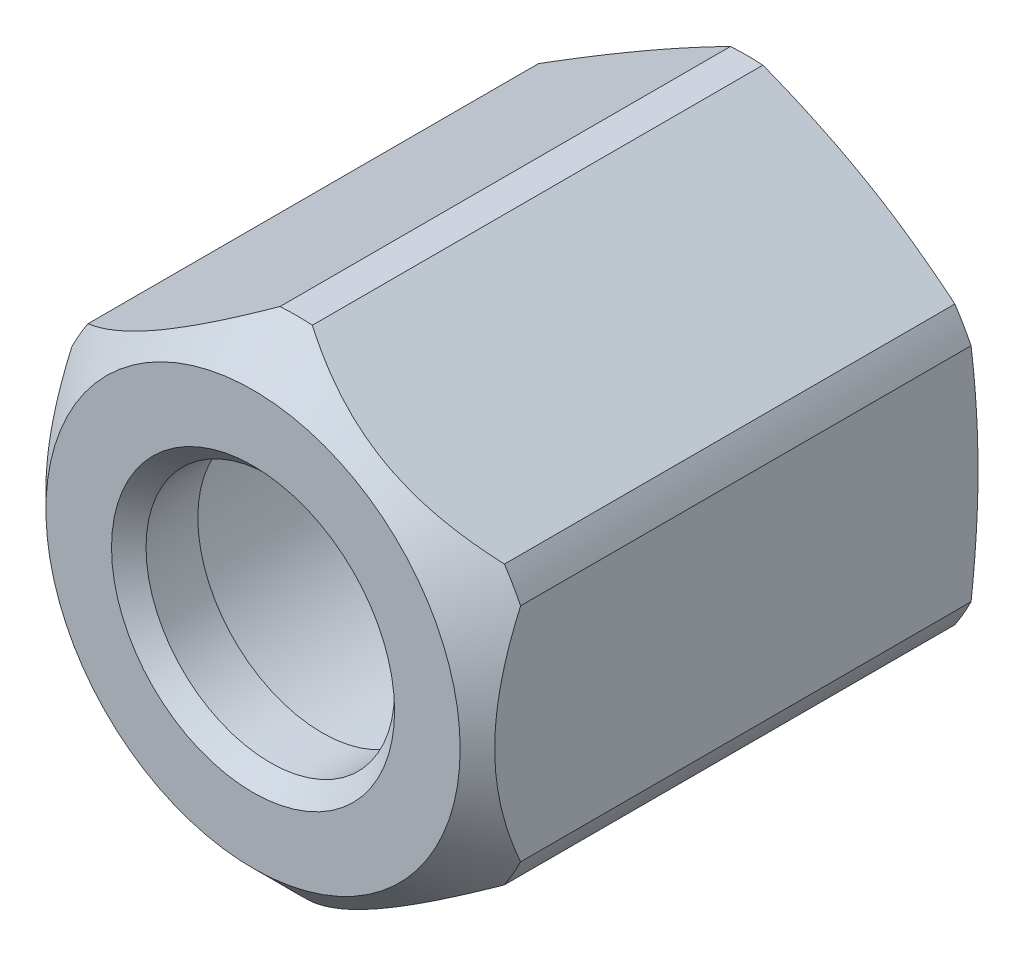
SolidWorks part; units mm, degrees
ref_plane "Ebene vorne" through (0, 0, 0) normal (0, 0, 1) x (1, 0, 0)
ref_plane "Ebene oben" through (0, 0, 0) normal (0, 1, 0) x (1, 0, 0)
ref_plane "Ebene rechts" through (0, 0, 0) normal (1, 0, 0) x (0, 0, -1)
sketch "Skizze1" plane through (0, 0, 0) normal (1, 0, 0) x (0, 0, -1)
  line L0 (0, 4.1) -> (0.5, 3.6)
  line L1 (0.5, 3.6) -> (2, 3.6)
  line L2 (2, 3.6) -> (2, 4.9)
  line L3 (2, 4.9) -> (10.8, 4.9)
  line L4 (10.8, 4.9) -> (10.8, 4.4585)
  line L5 (10.8, 4.4585) -> (13.9585, 4.4585)
  line L6 (13.9585, 4.4585) -> (14.5, 5)
  line L7 (14.5, 5) -> (14.5, 6.5)
  line L8 (14.5, 6.5) -> (14.299, 7.25)
  line L9 (14.299, 7.25) -> (1.25, 7.25)
  line L10 (1.25, 7.25) -> (0, 6)
  line L11 (0, 6) -> (0, 4.1)
  line L12 (14.5, 0) -> (0, 0) construction
revolve "Rotation1" add sketch "Skizze1" angle 360 about L12 reverse direction yes
cosmetic thread "Gewindedarstellung1" parameters "D1"=3.7, "D2"=10
sketch "Skizze2" plane through (0, 0, 0) normal (0, 0, 1) x (1, 0, 0)
  line L0 (-34.75, -33.8333) -> (32.5833, -33.8333)
  line L1 (32.5833, -33.8333) -> (32.5833, 34.1667)
  line L2 (32.5833, 34.1667) -> (-34.75, 34.1667)
  line L3 (-34.75, 34.1667) -> (-34.75, -33.8333)
  line L4 (-6.5, -3.7528) -> (0, -7.5056)
  line L5 (0, -7.5056) -> (6.5, -3.7528)
  line L6 (6.5, -3.7528) -> (6.5, 3.7528)
  line L7 (6.5, 3.7528) -> (0, 7.5056)
  line L8 (0, 7.5056) -> (-6.5, 3.7528)
  line L9 (-6.5, 3.7528) -> (-6.5, -3.7528)
extrude "Schnitt-Linear austragen1" cut sketch "Skizze2" along normal blind 30 and the other way blind 30
ref_plane "Ebene1" through (0, 0, -21.9) normal (0, 0, 1) x (1, 0, 0)
ref_plane "Ebene2" through (0, 0, -17.5) normal (0, 0, 1) x (1, 0, 0)
ref_plane "Ebene3" through (0, 0, -2) normal (0, 0, 1) x (1, 0, 0)
ref_plane "Ebene4" through (0, 0, -10.4) normal (0, 0, 1) x (1, 0, 0)
ref_plane "Ebene5" through (0, 0, 9.1) normal (0, 0, 1) x (1, 0, 0)
ref_plane "MUTTER XY" through (0, 0, 9.1) normal (0, 0, 1) x (1, 0, 0)
ref_plane "MUTTER XZ" through (0, 0, 0) normal (0, -1, 0) x (-1, 0, 0)
ref_plane "MUTTER YZ" through (0, 0, 0) normal (1, 0, 0) x (0, 0, -1)
ref_axis "MUTTER X" through (-80.9, 0, 9.1) along (1, 0, 0)
ref_axis "MUTTER Y" through (0, -50, 9.1) along (0, 1, 0)
ref_axis "MUTTER Z" through (0, 0, 80.9) along (0, 0, -1)
sketch3d "MUTTER"
  point P0 (0, 0, 9.1)
ref_plane "TO_DUMMY XY" through (0, 0, 0) normal (0, 1, 0) x (1, 0, 0)
ref_plane "TO_DUMMY XZ" through (0, 0, 0) normal (0, 0, 1) x (1, 0, 0)
ref_plane "TO_DUMMY YZ" through (0, 0, 0) normal (1, 0, 0) x (0, 0, -1)
ref_axis "TO_DUMMY X" through (-80.9, 0, 0) along (1, 0, 0)
ref_axis "TO_DUMMY Y" through (0, 0, 50) along (0, 0, -1)
ref_axis "TO_DUMMY Z" through (0, 50, 0) along (0, -1, 0)
sketch3d "TO_DUMMY"
  point P0 (0, 0, 0)
ref_plane "gehaeuse XY" through (0, 0, 0) normal (1, 0, 0) x (0, 0, -1)
ref_plane "gehaeuse XZ" through (0, 0, 0) normal (0, -1, 0) x (-1, 0, 0)
ref_plane "gehaeuse YZ" through (0, 0, -6.2) normal (0, 0, -1) x (-1, 0, 0)
ref_axis "gehaeuse X" through (0, 0, 80.9) along (0, 0, -1)
ref_axis "gehaeuse Y" through (0, -50, -6.2) along (0, 1, 0)
ref_axis "gehaeuse Z" through (80.9, 0, -6.2) along (-1, 0, 0)
sketch3d "gehaeuse"
  point P0 (0, 0, -6.2)
ref_plane "punkt_1_kugel XY" through (0, 0, -2) normal (0, 0, 1) x (1, 0, 0)
ref_plane "punkt_1_kugel XZ" through (0, 0, 0) normal (0, -1, 0) x (-1, 0, 0)
ref_plane "punkt_1_kugel YZ" through (0, 0, 0) normal (1, 0, 0) x (0, 0, -1)
ref_axis "punkt_1_kugel X" through (-80.9, 0, -2) along (1, 0, 0)
ref_axis "punkt_1_kugel Y" through (0, -50, -2) along (0, 1, 0)
ref_axis "punkt_1_kugel Z" through (0, 0, 80.9) along (0, 0, -1)
sketch3d "punkt_1_kugel"
  point P0 (0, 0, -2)
ref_plane "punkt_2_kugel XY" through (0, 0, -10.4) normal (0, 0, 1) x (1, 0, 0)
ref_plane "punkt_2_kugel XZ" through (0, 0, 0) normal (0, -1, 0) x (-1, 0, 0)
ref_plane "punkt_2_kugel YZ" through (0, 0, 0) normal (1, 0, 0) x (0, 0, -1)
ref_axis "punkt_2_kugel X" through (-80.9, 0, -10.4) along (1, 0, 0)
ref_axis "punkt_2_kugel Y" through (0, -50, -10.4) along (0, 1, 0)
ref_axis "punkt_2_kugel Z" through (0, 0, 80.9) along (0, 0, -1)
sketch3d "punkt_2_kugel"
  point P0 (0, 0, -10.4)
ref_plane "punkt_buchse XY" through (0, 0, -21.9) normal (0, 0, 1) x (1, 0, 0)
ref_plane "punkt_buchse XZ" through (0, 0, 0) normal (0, -1, 0) x (-1, 0, 0)
ref_plane "punkt_buchse YZ" through (0, 0, 0) normal (1, 0, 0) x (0, 0, -1)
ref_axis "punkt_buchse X" through (-80.9, 0, -21.9) along (1, 0, 0)
ref_axis "punkt_buchse Y" through (0, -50, -21.9) along (0, 1, 0)
ref_axis "punkt_buchse Z" through (0, 0, 80.9) along (0, 0, -1)
sketch3d "punkt_buchse"
  point P0 (0, 0, -21.9)
ref_plane "punkt_mutter XY" through (0, 0, -17.5) normal (0, 0, 1) x (1, 0, 0)
ref_plane "punkt_mutter XZ" through (0, 0, 0) normal (0, -1, 0) x (-1, 0, 0)
ref_plane "punkt_mutter YZ" through (0, 0, 0) normal (1, 0, 0) x (0, 0, -1)
ref_axis "punkt_mutter X" through (-80.9, 0, -17.5) along (1, 0, 0)
ref_axis "punkt_mutter Y" through (0, -50, -17.5) along (0, 1, 0)
ref_axis "punkt_mutter Z" through (0, 0, 80.9) along (0, 0, -1)
sketch3d "punkt_mutter"
  point P0 (0, 0, -17.5)
